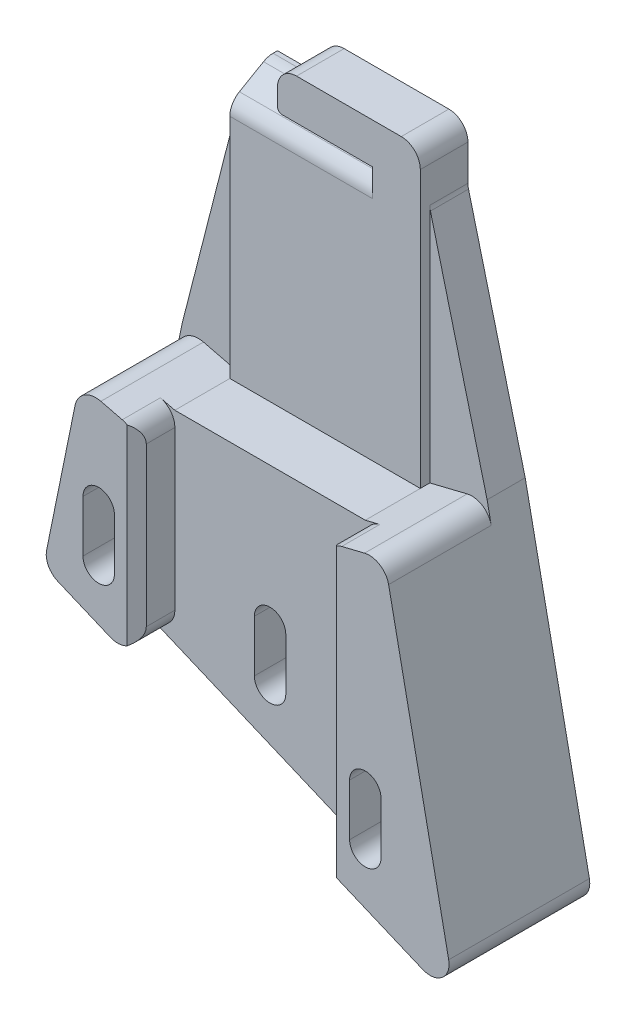
SolidWorks part; units mm, degrees
ref_plane "Front Plane" through (0, 0, 0) normal (0, 0, 1) x (1, 0, 0)
ref_plane "Top Plane" through (0, 0, 0) normal (0, 1, 0) x (1, 0, 0)
ref_plane "Right Plane" through (0, 0, 0) normal (1, 0, 0) x (0, 0, -1)
sketch "Sketch1" plane through (0, 0, 0) normal (0, 0, 1) x (1, 0, 0)
  line L0 (0, 0) -> (10, 0) construction
  line L1 (0, 0) -> (0, 10) construction
  line L2 (-143.3708, 41.2466) -> (77.8135, -51.9066) construction
  line L3 (74.9025, -58.8186) -> (-146.2818, 34.3346) construction
  line L4 (71.9914, -65.7306) -> (-149.1928, 27.4226) construction
  line L5 (-143.3708, 41.2466) -> (77.8135, -51.9066) construction
  line L6 (74.9025, -58.8186) -> (-146.2818, 34.3346) construction
  line L7 (71.9914, -65.7306) -> (-149.1928, 27.4226) construction
  line L8 (5, 15) -> (-5, 15) construction
  line L9 (-5, 16) -> (5, 16) construction
  line L10 (5, 16) -> (5, 15) construction
  line L11 (-5, 15) -> (-5, 16) construction
  line L12 (12.35, -30.4565) -> (12.35, -35.8818) construction
  line L13 (15.65, -35.8818) -> (15.65, -30.4565) construction
  line L14 (1.65, -24.5603) -> (1.65, -29.9856) construction
  line L15 (-1.65, -29.9856) -> (-1.65, -24.5603) construction
  line L16 (-12.35, -24.0894) -> (-12.35, -18.6641) construction
  line L17 (-15.65, -18.6641) -> (-15.65, -24.0894) construction
  line L18 (5, 15) -> (-5, 15) construction
  line L19 (-5, 16) -> (5, 16) construction
  line L20 (5, 16) -> (5, 15) construction
  line L21 (-5, 15) -> (-5, 16) construction
  line L22 (12.35, -30.4565) -> (12.35, -35.8818) construction
  line L23 (15.65, -35.8818) -> (15.65, -30.4565) construction
  line L24 (1.65, -24.5603) -> (1.65, -29.9856) construction
  line L25 (-1.65, -29.9856) -> (-1.65, -24.5603) construction
  line L26 (-12.35, -24.0894) -> (-12.35, -18.6641) construction
  line L27 (-15.65, -18.6641) -> (-15.65, -24.0894) construction
  circle A0 centre (0, 0) radius 10 construction
  circle A1 centre (0, 0) radius 10 construction
  circle A2 centre (0, 72.5) radius 82.5 construction
  circle A3 centre (0, 72.5) radius 82.5 construction
  arc A4 (15.65, -30.4565) -> (12.35, -30.4565) centre (14, -30.4565) ccw construction
  arc A5 (12.35, -35.8818) -> (15.65, -35.8818) centre (14, -35.8818) ccw construction
  arc A6 (-1.65, -29.9856) -> (1.65, -29.9856) centre (0, -29.9856) ccw construction
  arc A7 (1.65, -24.5603) -> (-1.65, -24.5603) centre (0, -24.5603) ccw construction
  arc A8 (-15.65, -24.0894) -> (-12.35, -24.0894) centre (-14, -24.0894) ccw construction
  arc A9 (-12.35, -18.6641) -> (-15.65, -18.6641) centre (-14, -18.6641) ccw construction
  circle A10 centre (-14, -18.6641) radius 4 construction
  circle A11 centre (0, -24.5603) radius 4 construction
  circle A12 centre (14, -30.4565) radius 4 construction
  arc A13 (15.65, -30.4565) -> (12.35, -30.4565) centre (14, -30.4565) ccw construction
  arc A14 (12.35, -35.8818) -> (15.65, -35.8818) centre (14, -35.8818) ccw construction
  arc A15 (-1.65, -29.9856) -> (1.65, -29.9856) centre (0, -29.9856) ccw construction
  arc A16 (1.65, -24.5603) -> (-1.65, -24.5603) centre (0, -24.5603) ccw construction
  arc A17 (-15.65, -24.0894) -> (-12.35, -24.0894) centre (-14, -24.0894) ccw construction
  arc A18 (-12.35, -18.6641) -> (-15.65, -18.6641) centre (-14, -18.6641) ccw construction
  circle A19 centre (-14, -18.6641) radius 4 construction
  circle A20 centre (0, -24.5603) radius 4 construction
  circle A21 centre (14, -30.4565) radius 4 construction
  dimension "D1" = 20
sketch "Sketch2" plane through (0, 0, 0) normal (0, 0, 1) x (1, 0, 0)
  line L0 (10, 21) -> (23.5124, -45.3134) construction
  line L1 (23.5124, -45.3134) -> (-19.7958, -27.0738) construction
  line L2 (-19.7958, -27.0738) -> (-10, 21) construction
  line L3 (-10, 21) -> (10, 21) construction
  line L4 (10, 21) -> (23.5124, -45.3134)
  line L5 (23.5124, -45.3134) -> (-19.7958, -27.0738)
  line L6 (-19.7958, -27.0738) -> (-10, 21)
  line L7 (-10, 21) -> (10, 21)
  line L8 (0, -35.411) -> (0, 21) construction
  line L9 (10, 21) -> (10, -10) construction
  line L10 (10, -10) -> (-10, -10) construction
  line L11 (-10, -10) -> (-10, 21) construction
  line L12 (10, -10) -> (16.0152, -8.52) construction
  line L13 (-10, -10) -> (-16.0152, -8.52) construction
  line L14 (-12.35, -24.0894) -> (-12.35, -18.6641) construction
  line L15 (-15.65, -18.6641) -> (-15.65, -24.0894) construction
  line L16 (-1.65, -29.9856) -> (-1.65, -24.5603) construction
  line L17 (1.65, -24.5603) -> (1.65, -29.9856) construction
  line L18 (12.35, -30.4565) -> (12.35, -35.8818) construction
  line L19 (15.65, -35.8818) -> (15.65, -30.4565) construction
  line L20 (-12.35, -24.0894) -> (-12.35, -18.6641)
  line L21 (-15.65, -18.6641) -> (-15.65, -24.0894)
  line L22 (-1.65, -29.9856) -> (-1.65, -24.5603)
  line L23 (1.65, -24.5603) -> (1.65, -29.9856)
  line L24 (12.35, -30.4565) -> (12.35, -35.8818)
  line L25 (15.65, -35.8818) -> (15.65, -30.4565)
  circle A0 centre (0, 0) radius 10 construction
  circle A1 centre (0, 0) radius 10 construction
  circle A2 centre (0, 72.5) radius 82.5 construction
  arc A3 (-15.65, -24.0894) -> (-12.35, -24.0894) centre (-14, -24.0894) ccw construction
  arc A4 (-12.35, -18.6641) -> (-15.65, -18.6641) centre (-14, -18.6641) ccw construction
  arc A5 (1.65, -24.5603) -> (-1.65, -24.5603) centre (0, -24.5603) ccw construction
  arc A6 (-1.65, -29.9856) -> (1.65, -29.9856) centre (0, -29.9856) ccw construction
  arc A7 (12.35, -35.8818) -> (15.65, -35.8818) centre (14, -35.8818) ccw construction
  arc A8 (15.65, -30.4565) -> (12.35, -30.4565) centre (14, -30.4565) ccw construction
  arc A9 (-15.65, -24.0894) -> (-12.35, -24.0894) centre (-14, -24.0894) ccw
  arc A10 (-12.35, -18.6641) -> (-15.65, -18.6641) centre (-14, -18.6641) ccw
  arc A11 (1.65, -24.5603) -> (-1.65, -24.5603) centre (0, -24.5603) ccw
  arc A12 (-1.65, -29.9856) -> (1.65, -29.9856) centre (0, -29.9856) ccw
  arc A13 (12.35, -35.8818) -> (15.65, -35.8818) centre (14, -35.8818) ccw
  arc A14 (15.65, -30.4565) -> (12.35, -30.4565) centre (14, -30.4565) ccw
sketch "Sketch3" plane through (0, 0, 0) normal (1, 0, 0) x (0, 0, -1)
  line L0 (0, 21) -> (0, -35.411) construction
  line L1 (0, -35.411) -> (-14.7752, -35.411) construction
  line L2 (-14.7752, -35.411) -> (-14.7752, 21) construction
  line L3 (-14.7752, 21) -> (0, 21) construction
  line L4 (-5, 21) -> (-5, -10)
  line L5 (-5, -10) -> (-10.7752, -10)
  line L6 (-10.7752, -10) -> (-10.7752, -35.411)
  line L7 (-10.7752, -35.411) -> (0, -35.411)
  line L8 (0, -10) -> (-14.7752, -10) construction
  line L11 (-11.8754, -10) -> (-11.8754, 21) construction
  line L12 (-6.6002, -10) -> (-6.6002, 21) construction
  line L13 (-10.2752, -10) -> (-10.2752, 21) construction
  line L14 (-11.8754, 5.5) -> (-10.2752, 5.5) construction
  line L15 (-6.6002, 5.5) -> (-5, 5.5) construction
  line L16 (-7.1002, 21) -> (-7.1002, -10) construction
  line L17 (-5, 21) -> (0, 21)
  line L18 (0, 21) -> (0, -35.411)
  dimension "D1" = 5
  dimension "D2" = 1.6002
  dimension "D3" = 0.5
  dimension "D4" = 3.175
  dimension "D5" = 0.5
  dimension "D6" = 4
extrude "Boss-Extrude1" add sketch "Sketch2" along normal up to vertex (14.7752 mm away) up to point (0, 21, 14.7752)
sketch "Sketch4" plane through (0, 0, 14.7752) normal (0, 0, 1) x (1, 0, 0)
  line L0 (-19.7958, -27.0738) -> (-10, 21) construction
  line L1 (-10, 21) -> (10, 21) construction
  line L2 (10, 21) -> (23.5124, -45.3134) construction
  line L3 (-16.0152, -8.52) -> (-10, 21)
  line L4 (-10, 21) -> (10, 21)
  line L5 (10, 21) -> (16.0152, -8.52)
  line L6 (10, -10) -> (-10, -10) construction
  line L7 (10, -10) -> (-10, -10)
  line L8 (10, -10) -> (16.0152, -8.52) construction
  line L9 (10, -10) -> (16.0152, -8.52)
  line L10 (-10, -10) -> (-16.0152, -8.52) construction
  line L11 (-10, -10) -> (-16.0152, -8.52)
extrude "Cut-Extrude1" cut sketch "Sketch4" against normal up to vertex (9.7752 mm away) up to point (0, 21, 5)
sketch "Sketch5" plane through (0, 0, 5) normal (0, 0, 1) x (1, 0, 0)
  line L0 (-10, -10) -> (-16.0152, -8.52)
  line L1 (-16.0152, -8.52) -> (-10, 21)
  line L2 (-10, 21) -> (-10, -10)
  line L3 (16.0152, -8.52) -> (10, -10)
  line L4 (10, -10) -> (10, 21)
  line L5 (10, 21) -> (16.0152, -8.52)
  line L6 (10, 21) -> (23.5124, -45.3134) construction
  line L7 (10, -10) -> (16.0152, -8.52) construction
  line L8 (-10, -10) -> (-16.0152, -8.52) construction
  line L9 (-10, -10) -> (-10, 21) construction
  line L10 (-19.7958, -27.0738) -> (-10, 21) construction
  line L11 (10, 21) -> (10, -10) construction
extrude "Cut-Extrude2" cut sketch "Sketch5" against normal blind 1
sketch "Sketch6" plane through (0, 0, 5) normal (0, 0, 1) x (1, 0, 0)
  line L0 (-16.0152, -8.52) -> (-10, 21) construction
  line L1 (10, 21) -> (16.0152, -8.52) construction
  line L2 (-16.0152, -8.52) -> (-10, 21)
  line L3 (10, 21) -> (16.0152, -8.52)
  line L4 (10, -10) -> (10, 21) construction
  line L5 (-10, 21) -> (-10, -10) construction
  line L6 (10, 15) -> (10, 21)
  line L7 (-10, 21) -> (-10, 15)
  line L8 (10, 15) -> (-10, 15) construction
  line L9 (5, 15) -> (-5, 15) construction
  line L10 (16.0152, -8.52) -> (10, 15)
  line L11 (-10, 15) -> (-16.0152, -8.52)
extrude "Cut-Extrude3" cut sketch "Sketch6" against normal through all
sketch "Sketch7" plane through (0, 0, 14.7752) normal (0, 0, 1) x (1, 0, 0)
  line L0 (23.5124, -45.3134) -> (-19.7958, -27.0738) construction
  line L1 (10, -39.6225) -> (-10, -31.1994)
  line L2 (-10, 21) -> (10, 21) construction
  line L3 (-10, 21) -> (10, 21)
  line L4 (10, 21) -> (10, -39.6225)
  line L5 (-10, 21) -> (-10, -31.1994)
  line L6 (10, 21) -> (10, -10) construction
  line L7 (-10, -10) -> (-10, 21) construction
extrude "Cut-Extrude4" cut sketch "Sketch7" against normal up to vertex (4 mm away) up to point (0, -10, 10.7752)
sketch "Sketch8" plane through (0, 0, 0) normal (1, 0, 0) x (0, 0, -1)
  line L0 (0, 15) -> (-5, 15) construction
  line L1 (0, 21) -> (0, -35.411) construction
  line L2 (0, 16) -> (-5, 16) construction
  line L3 (-5, 21) -> (-5, -10) construction
  line L4 (-5, 21) -> (0, 21) construction
  line L5 (-5, 21) -> (-5, -10) construction
  line L6 (0, 21) -> (0, -35.411) construction
  line L7 (-5, 21) -> (0, 21) construction
  line L8 (-5, 15) -> (-1, 17.3094)
  line L9 (-1, 17.3094) -> (0, 17.3094)
  line L10 (-5, 16.1547) -> (0, 19.0415) construction
  line L11 (-4, 16.7321) -> (-5, 16.7321)
  line L12 (0, 19.0415) -> (0, 17.3094)
  line L13 (-4, 16.7321) -> (0, 19.0415)
  line L14 (-5, 15) -> (-5, 16.7321)
  dimension "D1" = 1
  dimension "D2" = 1
  dimension "D3" = 30
extrude "Cut-Extrude5" cut sketch "Sketch8" along normal up to vertex (5 mm away) and the other way through all up to point (5, 15, 0)
sketch "Sketch9" plane through (-10, 0, 0) normal (-1, 0, 0) x (0, 0, 1)
  line L4 (0, 19.0415) -> (4, 16.7321)
  line L5 (5, 16.7321) -> (5, 21)
  line L6 (5, 21) -> (0, 21)
  line L7 (0, 21) -> (0, 19.0415)
  line L8 (0, 19.0415) -> (4, 16.7321)
  line L9 (5, 16.7321) -> (5, 21)
  line L10 (5, 21) -> (0, 21)
  line L11 (0, 21) -> (0, 19.0415)
  line L13 (4, 16.7321) -> (5, 16.7321)
  line L14 (4, 16.7321) -> (5, 16.7321)
  dimension "D1" = 0
extrude "Cut-Extrude6" cut sketch "Sketch9" against normal up to vertex (5 mm away) up to point (-5, 16, 0)
chamfer "Chamfer1" distance 1 angle 45 2 edges at (-10, -20.5997, 14.7752) (10, -24.8113, 14.7752)
fillet "Fillet1" radius 2 10 edges at (10, 15, 2) (-10, 15, 2) (-5, 21, 2.5) (10, 21, 2.5) (-10, -10, 12.2752) (10, -10, 12.2752) (-10, -31.1994, 12.2752) (10, -39.6225, 12.2752) (-19.7958, -27.0738, 7.3876) (23.5124, -45.3134, 7.3876)
fillet "Fillet2" radius 2 3 edges at (-2.5, 15, 5) (0, 16.7321, 4) (-2.5, 17.3094, 1)
fillet "Fillet3" radius 0.5 4 edges at (-4.9999, 19.0207, 0.0359) (-5, 16.7321, 4.7679) (-5, 16.8002, 4.0183) (-5, 18, 1.8038)
sketch "Sketch10" plane through (0, 0, 14.7752) normal (0, 0, 1) x (1, 0, 0)
  line L0 (-16.0152, -8.52) -> (-19.4685, -25.4676) construction
  line L1 (-16.0152, -8.52) -> (-11.5222, -9.6255) construction
  line L2 (-16.0152, -8.52) -> (-16.477, -10.7867)
  line L3 (-16.0152, -8.52) -> (-13.769, -9.0727)
  line L4 (22.7557, -41.5999) -> (16.0152, -8.52) construction
  line L5 (11.5222, -9.6255) -> (16.0152, -8.52) construction
  line L6 (16.4457, -10.6329) -> (16.0152, -8.52)
  line L7 (13.9214, -9.0352) -> (16.0152, -8.52)
  arc A0 (16.4457, -10.6329) -> (13.9214, -9.0352) centre (14.4162, -11.0464) ccw
  arc A1 (-13.769, -9.0727) -> (-16.477, -10.7867) centre (-14.2998, -11.2303) ccw
extrude "Cut-Extrude7" cut sketch "Sketch10" against normal up to surface (10.7752 mm away) up to face at (11.5155, 2.8715, 4)
